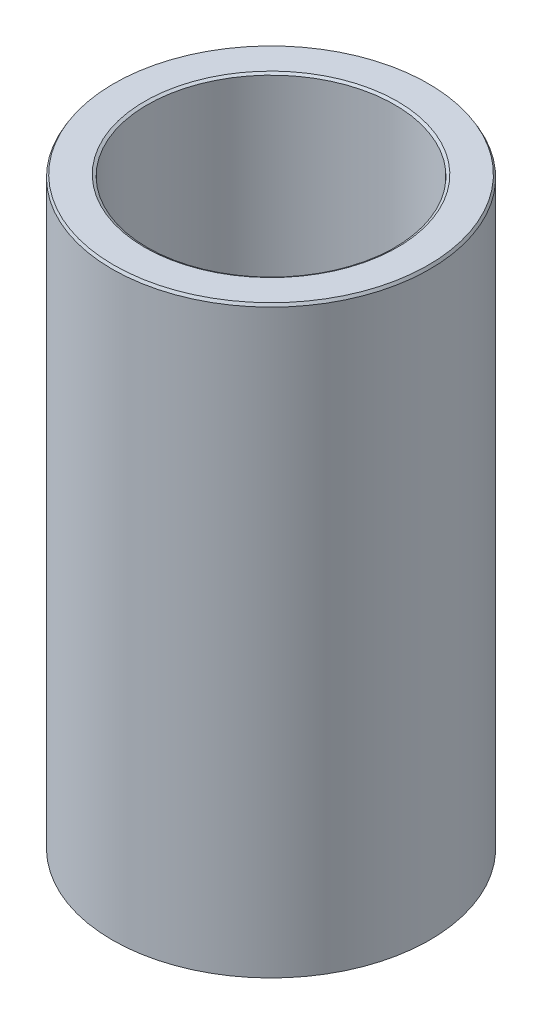
SolidWorks part; units mm, degrees
ref_plane "Front Plane" through (0, 0, 0) normal (0, 0, 1) x (1, 0, 0)
ref_plane "Top Plane" through (0, 0, 0) normal (0, 1, 0) x (1, 0, 0)
ref_plane "Right Plane" through (0, 0, 0) normal (1, 0, 0) x (0, 0, -1)
sketch "Sketch1" plane through (0, 0, 0) normal (0, 1, 0) x (1, 0, 0)
  circle A0 centre (0, 0) radius 50
  dimension "SLEEVE_OD" = 100
extrude "Boss-Extrude1" add sketch "Sketch1" along normal blind 184.2442
sketch "Sketch2" plane through (0, 0, 0) normal (0, 1, 0) x (1, 0, 0)
  circle A0 centre (0, 0) radius 38.9433
  dimension "BORE_D" = 77.8866
extrude "Cut-Extrude1" cut sketch "Sketch2" along normal through all
chamfer "Chamfer1" distance 0.8588 angle 30 4 edges at (0, 184.2442, 38.9433) (0, 0, 38.9433) (0, 0, 50) (0, 184.2442, 50) first distance on face at (0, 184.2442, 38.9433) first distance on face at (0, 0, 38.9433) first distance on face at (0, 184.2442, 50)
